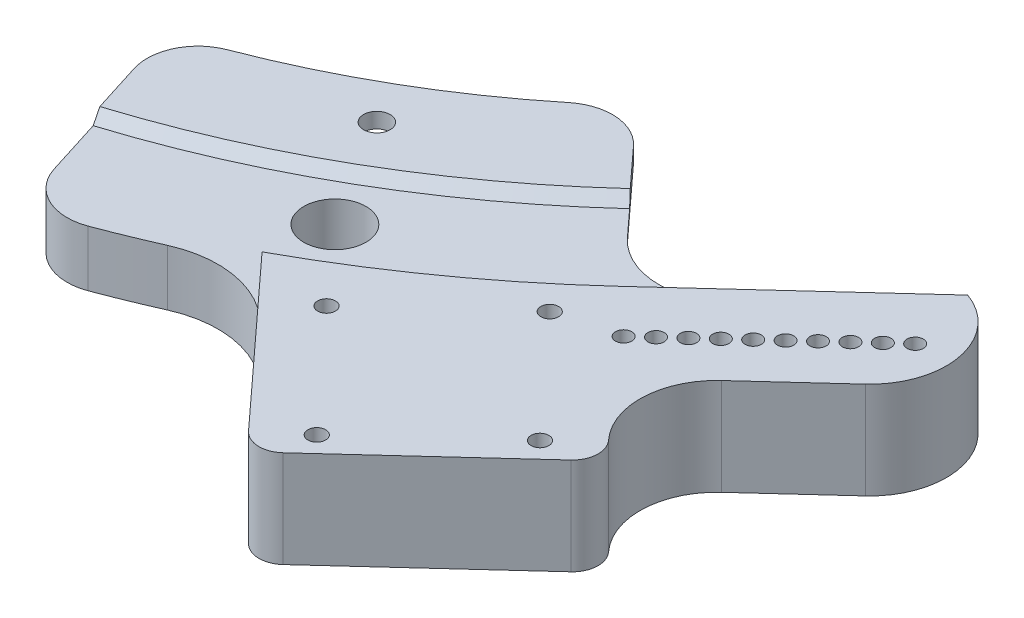
SolidWorks part; units mm, degrees
ref_plane "Спереди" through (0, 0, 0) normal (0, 0, 1) x (1, 0, 0)
ref_plane "Сверху" through (0, 0, 0) normal (0, 1, 0) x (1, 0, 0)
ref_plane "Справа" through (0, 0, 0) normal (1, 0, 0) x (0, 0, -1)
sketch "Эскиз1" plane through (0, 0, 0) normal (0, 1, 0) x (1, 0, 0)
  line L0 (94, -162.8128) -> (82.75, -143.3272) construction
  line L1 (82.75, -143.3272) -> (0, 0) construction
  line L2 (0, 0) -> (251.0551, 0) construction
  circle A1 centre (0, 0) radius 156
  circle A3 centre (0, 0) radius 200
  circle A5 centre (82.75, -143.3272) radius 2.6
  circle A7 centre (94, -162.8128) radius 6.1
  circle A9 centre (0, 0) radius 175
  point P0 (0, 0)
  point P4 (0, 5.1193)
  dimension "D1" = 312
  dimension "D2" = 350
  dimension "D3" = 400
  dimension "D4" = 12.2
  dimension "D5" = 5.2
  dimension "D6" = 165.5
  dimension "D7" = 22.5
  dimension "D8" = 60
extrude "Бобышка-Вытянуть1" add sketch "Эскиз1" along normal blind 2 contours A9 A1 A5 region at (-170.0503, 0, 0)
extrude "Бобышка-Вытянуть3" add sketch "Эскиз1<5>" against normal blind 1 contours A9 A1 A5 region at (-170.0503, 0, 0)
sketch "Эскиз1<5>" plane through (0, 0, 0) normal (0, 1, 0) x (1, 0, 0) same geometry as "Эскиз1"
extrude "Бобышка-Вытянуть4" add sketch "Эскиз1<6>" against normal blind 11 contours A3 A9 A7 region at (-194.3431, 0, 0)
sketch "Эскиз1<6>" plane through (0, 0, 0) normal (0, 1, 0) x (1, 0, 0) same geometry as "Эскиз1"
sketch "Эскиз3" plane through (0, 2, 0) normal (0, 1, 0) x (1, 0, 0)
  line L0 (0, 0) -> (60.1412, -190.7434)
  line L1 (0, 0) -> (135.118, -147.4555)
  line L2 (0, 0) -> (100, -173.2051) construction
  circle A0 centre (0, 0) radius 200 construction
  arc A1 (135.118, -147.4555) -> (60.1412, -190.7434) centre (0, 0) ccw
  circle A4 centre (94, -162.8128) radius 6.1 construction
  point P1 (0, 0)
  point P10 (94, -162.8128)
  dimension "D1" = 25
  dimension "D2" = 12.5
extrude "Вырез-Вытянуть1" cut sketch "Эскиз3" against normal through all
fillet "Скругление2" radius 10 3 edges at (46.9101, 0.5, 148.7798) (60.1412, -5.5, 190.7434) (105.3921, 0.5, 115.0153)
ref_plane "Плоскость1" through (0, 8, 0) normal (0, 1, 0) x (1, 0, 0)
sketch "Эскиз5" plane through (0, 8, 0) normal (0, 1, 0) x (1, 0, 0)
  line L0 (135.118, -147.4555) -> (168.8976, -184.3193)
  line L1 (168.8976, -184.3193) -> (132.0337, -218.0988)
  line L2 (132.0337, -218.0988) -> (93.9636, -176.5527)
  line L4 (118.2283, -129.0235) -> (135.118, -147.4555) construction
  arc A0 (70.0969, -187.3137) -> (135.118, -147.4555) centre (0, 0) ccw construction
  arc A3 (93.9636, -176.5527) -> (135.118, -147.4555) centre (0, 0) ccw
  dimension "D1" = 50
  dimension "D2" = 50
extrude "Бобышка-Вытянуть5" add sketch "Эскиз5" against normal up to surface (19 mm away) contours A3 L2 L1 L0 region at (132.469, 8, 182.3185) up to face at (94, -11, 168.9128)
fillet "Скругление9" radius 20 1 edges at (93.9636, -5.5, 176.5527)
chamfer "Фаска3" distance 3 angle 45 1 edges at (87.5, 0, 151.5544)
sketch "Эскиз10" plane through (0, 8, 0) normal (0, 1, 0) x (1, 0, 0)
  line L0 (135.9977, -208.363) -> (158.8533, -187.4197) construction
  line L1 (158.8533, -187.4197) -> (137.91, -164.5641) construction
  line L2 (137.91, -164.5641) -> (115.0544, -185.5074) construction
  line L3 (115.0544, -185.5074) -> (135.9977, -208.363) construction
  line L4 (168.8976, -184.3193) -> (132.0337, -218.0988) construction
  line L5 (135.118, -147.4555) -> (168.8976, -184.3193) construction
  line L7 (125.526, -196.9352) -> (118.5219, -203.3533) construction
  line L8 (132.0337, -218.0988) -> (93.9636, -176.5527) construction
  line L9 (148.3816, -175.9919) -> (155.3857, -169.5738) construction
  circle A0 centre (137.91, -164.5641) radius 1.75
  circle A1 centre (115.0544, -185.5074) radius 1.75
  circle A2 centre (158.8533, -187.4197) radius 1.75
  circle A3 centre (135.9977, -208.363) radius 1.75
  point P18 (0, 0)
  point P19 (121.4156, -206.5113)
  point P20 (0, 0)
  point P21 (0, 0)
  dimension "D5" = 3.5
  dimension "D6" = 3.5
  dimension "D7" = 3.5
  dimension "D8" = 3.5
  dimension "D1" = 31
  dimension "D2" = 20
  dimension "D4" = 31
extrude "Вырез-Вытянуть5" cut sketch "Эскиз10" against normal through all
fillet "Скругление11" radius 5 1 edges at (132.0337, -1.5, 218.0988)
sketch "Эскиз12" plane through (0, 8, 0) normal (0, 1, 0) x (1, 0, 0)
  line L0 (135.118, -147.4555) -> (171.9819, -113.676)
  line L1 (171.9819, -113.676) -> (205.7614, -150.5398)
  line L2 (205.7614, -150.5398) -> (168.8976, -184.3193)
  line L3 (168.8976, -184.3193) -> (135.7201, -214.7209) construction
  line L4 (135.118, -147.4555) -> (168.8976, -184.3193) construction
  line L5 (135.118, -147.4555) -> (168.8976, -184.3193)
  dimension "D1" = 50
extrude "Бобышка-Вытянуть6" add sketch "Эскиз12" against normal up to surface (19 mm away) up to face at (137.91, -11, 166.3141)
chamfer "Фаска2" distance 8 angle 45 2 edges at (115.4611, 8, 163.3057) (153.55, 8, 130.5657)
fillet "Скругление12" radius 15 1 edges at (135.118, -5.5, 147.4555)
fillet "Скругление13" radius 15 1 edges at (118.2283, -6, 129.0235)
sketch "Эскиз13" plane through (0, 8, 0) normal (0, 1, 0) x (1, 0, 0)
  line L0 (149.3671, -161.5254) -> (181.8073, -131.7995) construction
  line L3 (177.3866, -119.5742) -> (140.5228, -153.3537) construction
  line L4 (146.1772, -137.3216) -> (171.9819, -113.676) construction
  line L5 (205.7614, -150.5398) -> (177.3866, -119.5742) construction
  line L6 (135.118, -147.4555) -> (140.5228, -153.3537) construction
  circle A2 centre (149.3671, -161.5254) radius 1.6
  circle A3 centre (152.6849, -158.4853) radius 1.6
  circle A4 centre (156.0026, -155.4451) radius 1.6
  circle A5 centre (159.3204, -152.405) radius 1.6
  circle A6 centre (162.6381, -149.3648) radius 1.6
  circle A7 centre (165.9559, -146.3246) radius 1.6
  circle A8 centre (169.2736, -143.2845) radius 1.6
  circle A9 centre (172.5914, -140.2443) radius 1.6
  circle A10 centre (175.9091, -137.2042) radius 1.6
  circle A11 centre (179.2269, -134.164) radius 1.6
  dimension "D4" = 3.2
  dimension "D1" = 20
  dimension "D2" = 5
  dimension "D3" = 1
extrude "Вырез-Вытянуть6" cut sketch "Эскиз13" against normal through all
sketch "Эскиз14" plane through (0, 8, 0) normal (0, 1, 0) x (1, 0, 0)
  line L0 (140.5228, -153.3537) -> (168.8976, -184.3193) construction
  line L1 (205.7614, -150.5398) -> (135.7201, -214.7209) construction
  line L2 (168.8976, -184.3193) -> (205.7614, -150.5398)
  line L3 (205.7614, -150.5398) -> (192.2496, -135.7943)
  line L4 (205.7614, -150.5398) -> (177.3866, -119.5742) construction
  line L5 (192.2496, -135.7943) -> (155.3857, -169.5738)
  line L6 (155.3857, -169.5738) -> (168.8976, -184.3193)
  dimension "D1" = 20
extrude "Вырез-Вытянуть7" cut sketch "Эскиз14" against normal through all
fillet "Скругление14" radius 15 3 edges at (155.3857, -1.5, 169.5738) (171.9819, -5.5, 113.676) (192.2496, -1.5, 135.7943)
fillet "Скругление15" radius 5 1 edges at (168.8976, -1.5, 184.3193)
